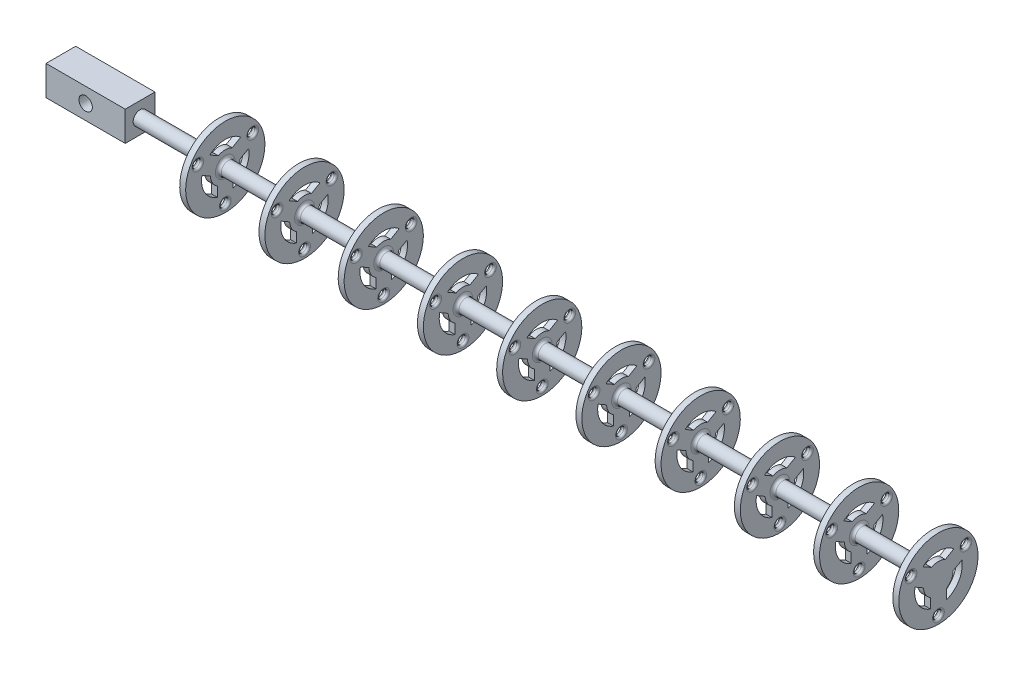
SolidWorks part; units mm, degrees
ref_plane "Front Plane" through (0, 0, 0) normal (0, 0, 1) x (1, 0, 0)
ref_plane "Top Plane" through (0, 0, 0) normal (0, 1, 0) x (1, 0, 0)
ref_plane "Right Plane" through (0, 0, 0) normal (1, 0, 0) x (0, 0, -1)
sketch "Sketch2" plane through (0, 0, 0) normal (0, 0, 1) x (1, 0, 0)
  line L0 (0, 1.75) -> (200, 1.75)
  line L1 (0, -11) -> (0, 11) construction
  line L2 (200, 1.75) -> (200, 0)
  line L3 (200, 0) -> (0, 0)
  line L4 (0, 0) -> (0, 1.75)
  dimension "D1" = 1.75
  dimension "D2" = 200
  dimension "D3" = 1.75
revolve "Revolve1" add sketch "Sketch2" angle 360 about L3
ref_axis "Axis1" through (-3.9062, 0, 0) along (1, 0, 0)
sketch "Sketch3" plane through (0, 0, 0) normal (0, 0, 1) x (1, 0, 0)
  line L0 (20, 0) -> (20, 10)
  line L1 (20, 10) -> (21.5, 10)
  line L2 (21.5, 10) -> (21.5, 0)
  line L3 (21.5, 0) -> (20, 0)
  line L4 (0, -11) -> (0, 11) construction
  dimension "D1" = 1.5
  dimension "D2" = 10
  dimension "D3" = 20
revolve "Revolve2" add sketch "Sketch3" angle 360 about L3
sketch "Sketch5" plane through (21.5, 0, 0) normal (1, 0, 0) x (0, 0, -1)
  line L0 (0, -8) -> (0, 0) construction
  line L1 (0, 0) -> (6.9282, 4) construction
  line L2 (-6.9282, 4) -> (0, 0) construction
  line L3 (0, 11) -> (0, -11) construction
  line L4 (-3.899, 4.5605) -> (-1.7472, 3.3181)
  line L5 (1.7472, 3.3181) -> (3.899, 4.5605)
  line L6 (2, -3.1721) -> (2, -5.6569)
  line L7 (5.899, 1.0964) -> (3.7472, -0.146)
  line L8 (-3.7472, -0.146) -> (-5.899, 1.0964)
  line L9 (-2, -5.6569) -> (-2, -3.1721)
  circle A0 centre (0, -8) radius 1
  circle A1 centre (6.9282, 4) radius 1
  circle A2 centre (-6.9282, 4) radius 1
  arc A3 (-3.899, 4.5605) -> (3.899, 4.5605) centre (0, 0) cw
  circle A6 centre (0, 0) radius 10 construction
  arc A8 (-1.7472, 3.3181) -> (1.7472, 3.3181) centre (0, 0) cw
  circle A9 centre (0, 0) radius 1.75 construction
  arc A10 (5.899, 1.0964) -> (2, -5.6569) centre (0, 0) cw
  arc A11 (3.7472, -0.146) -> (2, -3.1721) centre (0, 0) cw
  arc A12 (-2, -5.6569) -> (-5.899, 1.0964) centre (0, 0) cw
  arc A13 (-2, -3.1721) -> (-3.7472, -0.146) centre (0, 0) cw
  point P29 (0, 0)
  dimension "D2" = 2
  dimension "D1" = 8
  dimension "D3" = 120
  dimension "D4" = 120
  dimension "D6" = 2
  dimension "D7" = 4
  dimension "D5" = 2
  dimension "D8" = 3
extrude "Cut-Extrude1" cut sketch "Sketch5" against normal up to next
fillet "Fillet1" radius 0.5 6 edges at (20, 3, -6.9282) (20, -9, 0) (21.5, -7, 0) (21.5, 5, -6.9282) (20, 3, 6.9282) (21.5, 5, 6.9282)
pattern_linear "LPattern1" count 10 spacing 20 along (1, 0, 0) of "Revolve2", "Cut-Extrude1", "Fillet1"
sketch "Sketch16" plane through (0, 0, 0) normal (-1, 0, 0) x (0, 0, 1)
  line L1 (-3.75, -3.75) -> (3.75, -3.75)
  line L2 (-3.75, -3.75) -> (-3.75, 3.75)
  line L3 (-3.75, 3.75) -> (3.75, 3.75)
  line L4 (3.75, -3.75) -> (3.75, 3.75)
  line L5 (-3.75, -3.75) -> (3.75, 3.75) construction
  line L6 (-3.75, 3.75) -> (3.75, -3.75) construction
  point P0 (0, 0)
  dimension "D1" = 7.5
extrude "Boss-Extrude1" add sketch "Sketch16" along normal blind 20
sketch "Sketch19" plane through (0, 0, -3.75) normal (0, 0, -1) x (-1, 0, 0)
  line L0 (3.9062, 0) -> (-200, 0) construction
  line L1 (20, 3.75) -> (0, 3.75) construction
  line L2 (20, 3.75) -> (20, -3.75) construction
  point P0 (10, 0)
  point P7 (10, 3.75)
  point P10 (20, 0)
hole_wizard "M3 Clearance Hole1" positions "Sketch19" profile "Sketch18" hole size "M3" standard "ANSI Metric" end condition through all
sketch "Sketch18" plane through (-10, 0, -3.75) normal (1, 0, 0) x (0, 1, 0)
  line L0 (0, 0) -> (0, 13.75)
  line L1 (0, 13.75) -> (1.7, 13.75)
  line L2 (1.7, 13.75) -> (1.7, 0.025)
  line L3 (1.7, 0.025) -> (1.725, 0)
  line L5 (1.725, 0) -> (0, 0)
  line L6 (-1.7, 0.025) -> (-1.725, 0) construction
  line L11 (0, -6.35) -> (0, 107.95) construction
  dimension "Thru Hole Dia." = 3.4
  dimension "Thru Hole Depth" = 13.75
  dimension "Near C'Sink Dia." = 3.45
  dimension "Near C'Sink Angle" = 90
fillet "Fillet2" radius 0.75 19 edges at (20, -1.75, 0) (21.5, 1.75, 0) (40, -1.75, 0) (41.5, 1.75, 0) (60, -1.75, 0) (61.5, 1.75, 0) (80, -1.75, 0) (81.5, 1.75, 0) (100, -1.75, 0) (101.5, 1.75, 0) (120, -1.75, 0) (121.5, 1.75, 0) (140, -1.75, 0) (141.5, 1.75, 0) (160, -1.75, 0) (161.5, 1.75, 0) (180, -1.75, 0) (181.5, 1.75, 0) (200, 1.75, 0)
equation "\"R_initial\" = 1.75"
equation "\"D1@Sketch2\"=\"R_initial\""
equation "\"R_distal\" = 1.75"
equation "\"D3@Sketch2\"=\"R_distal\""
equation "\"L\"=200"
equation "\"D2@Sketch2\"=\"L\""
equation "\"disk_thickness\"= 1.5"
equation "\"D1@Sketch3\"=\"disk_thickness\""
equation "\"disk_radius\"= 10"
equation "\"D2@Sketch3\"=\"disk_radius\""
equation "\"disk_spacing_initial\"= 20"
equation "\"D3@Sketch3\"=\"disk_spacing_initial\""
equation "\"tendon_routing_radius\"= 8"
equation "\"D1@Sketch5\"=\"tendon_routing_radius\""
equation "\"tendon_routing_hole_radius\"=2"
equation "\"D2@Sketch5\"=\"tendon_routing_hole_radius\""
equation "\"tendon_routing_hole_fillet\"=0.5"
equation "\"D1@Fillet1\"=\"tendon_routing_hole_fillet\""
equation "\"inter_disk_spacing\"= 20"
equation "\"D3@LPattern1\"=\"inter_disk_spacing\""
equation "\"num_disk\"= 10"
equation "\"D1@LPattern1\"=\"num_disk\""
